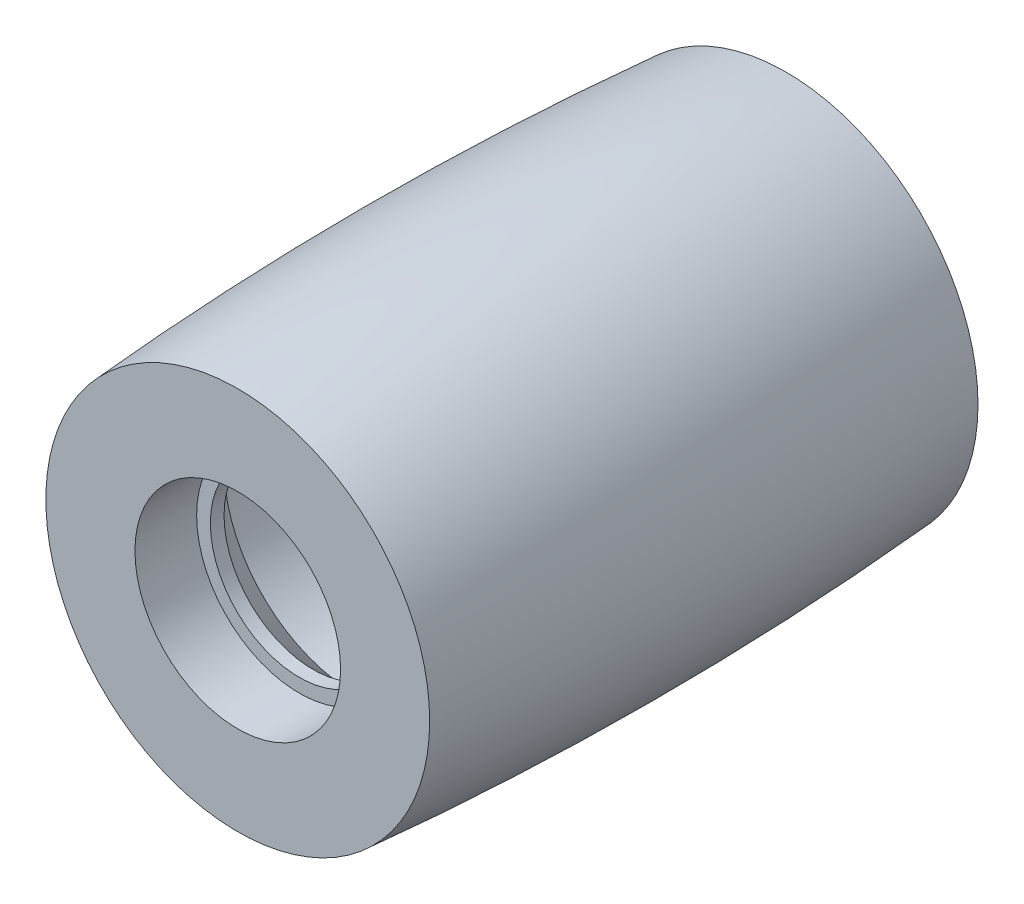
SolidWorks part; units mm, degrees
ref_plane "Ebene vorne" through (0, 0, 0) normal (0, 0, 1) x (1, 0, 0)
ref_plane "Ebene oben" through (0, 0, 0) normal (0, 1, 0) x (1, 0, 0)
ref_plane "Ebene rechts" through (0, 0, 0) normal (1, 0, 0) x (0, 0, -1)
sketch "Skizze1" plane through (0, 0, 0) normal (1, 0, 0) x (0, 0, -1)
  line L0 (10, 28) -> (10, 15) construction
  line L1 (19, 15) -> (10, 15) construction
  line L2 (19, 15) -> (19, 5) construction
  line L3 (19, 13) -> (21, 13) construction
  line L4 (21, 13) -> (34, 26) construction
  line L5 (21, 19.25) -> (43.3, 19.25) construction
  line L6 (43.3, 11) -> (43.3, 19.25) construction
  line L7 (46.3, 11) -> (43.3, 11) construction
  line L8 (46.3, 19.25) -> (46.3, 11) construction
  line L9 (46.3, 19.25) -> (85, 19.25) construction
  line L10 (85, 19.25) -> (87.1445, 20.25) construction
  line L11 (87.1445, 20.25) -> (90, 20.25) construction
  line L12 (90, 28) -> (90, 20.25) construction
  line L13 (10, 28) -> (10, 15)
  line L14 (19, 15) -> (10, 15)
  line L15 (19, 15) -> (19, 13)
  line L16 (19, 13) -> (21, 13)
  line L17 (21, 13) -> (27.25, 19.25)
  line L18 (27.25, 19.25) -> (43.3, 19.25)
  line L19 (43.3, 11) -> (43.3, 19.25)
  line L20 (46.3, 11) -> (43.3, 11)
  line L21 (46.3, 19.25) -> (46.3, 11)
  line L22 (46.3, 19.25) -> (85, 19.25)
  line L23 (85, 19.25) -> (87.1445, 20.25)
  line L24 (87.1445, 20.25) -> (90, 20.25)
  line L25 (90, 28) -> (90, 20.25)
  line L26 (0, 0) -> (100, 0) construction
  line L27 (0, 0) -> (100, 0) construction
  arc A0 (90, 28) -> (10, 28) centre (50, -504.5833) ccw construction
  arc A1 (90, 28) -> (10, 28) centre (50, -504.5833) ccw
revolve "Rotation1" add sketch "Skizze1" angle 360 about L27
